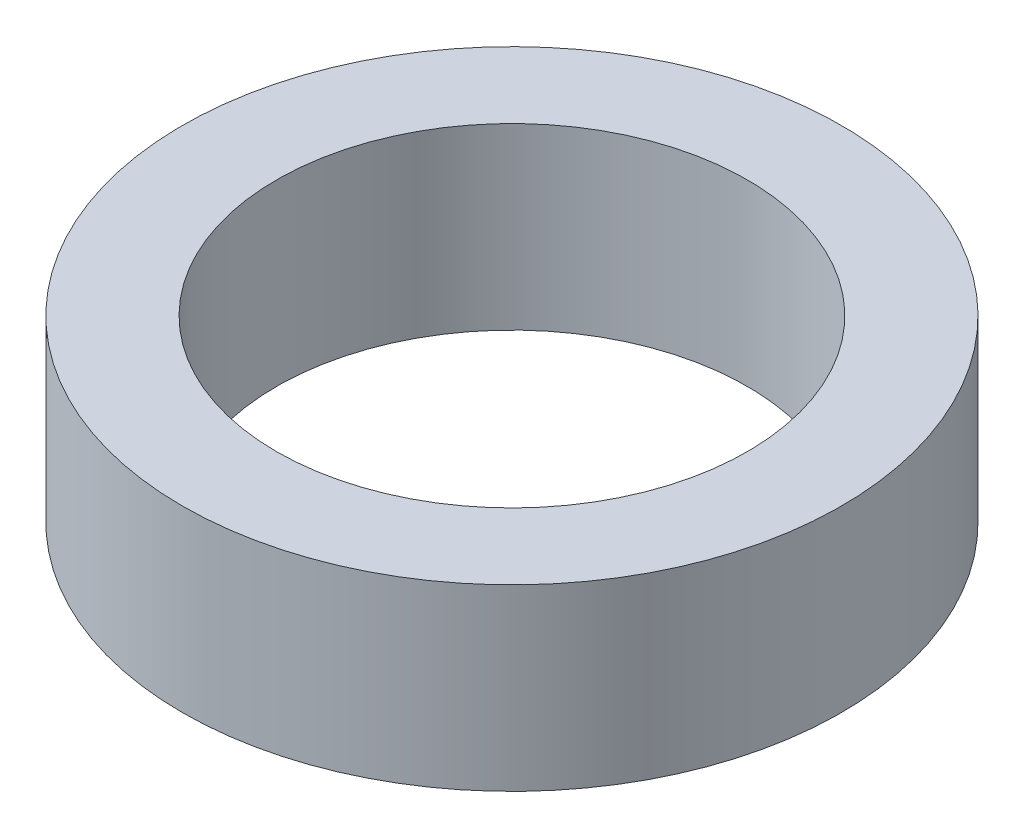
SolidWorks part; units mm, degrees
ref_plane "Front Plane" through (0, 0, 0) normal (0, 0, 1) x (1, 0, 0)
ref_plane "Top Plane" through (0, 0, 0) normal (0, 1, 0) x (1, 0, 0)
ref_plane "Right Plane" through (0, 0, 0) normal (1, 0, 0) x (0, 0, -1)
sketch "Sketch1" plane through (0, 0, 0) normal (0, 1, 0) x (1, 0, 0)
  circle A0 centre (0, 0) radius 35
  dimension "FLANGE_OD" = 70
extrude "Boss-Extrude1" add sketch "Sketch1" along normal blind 19
sketch "Sketch2" plane through (0, 0, 0) normal (0, 1, 0) x (1, 0, 0)
  circle A0 centre (0, 0) radius 25
  dimension "BORE_D" = 50
extrude "Cut-Extrude1" cut sketch "Sketch2" along normal through all
sketch "Sketch3" plane through (0, 19, 0) normal (0, 1, 0) x (1, 0, 0)
  circle A0 centre (0, 0) radius 14.9987 construction
  circle A1 centre (-14.9987, 0) radius 1.5072
  dimension "BOLT_D" = 3.0144
  dimension "BOLT_PCD" = 29.9974
extrude "Cut-Extrude2" cut sketch "Sketch3" against normal blind 13.855 rebuild error yes
pattern_circular "CirPattern1" count 6 over 360 rebuild error yes
